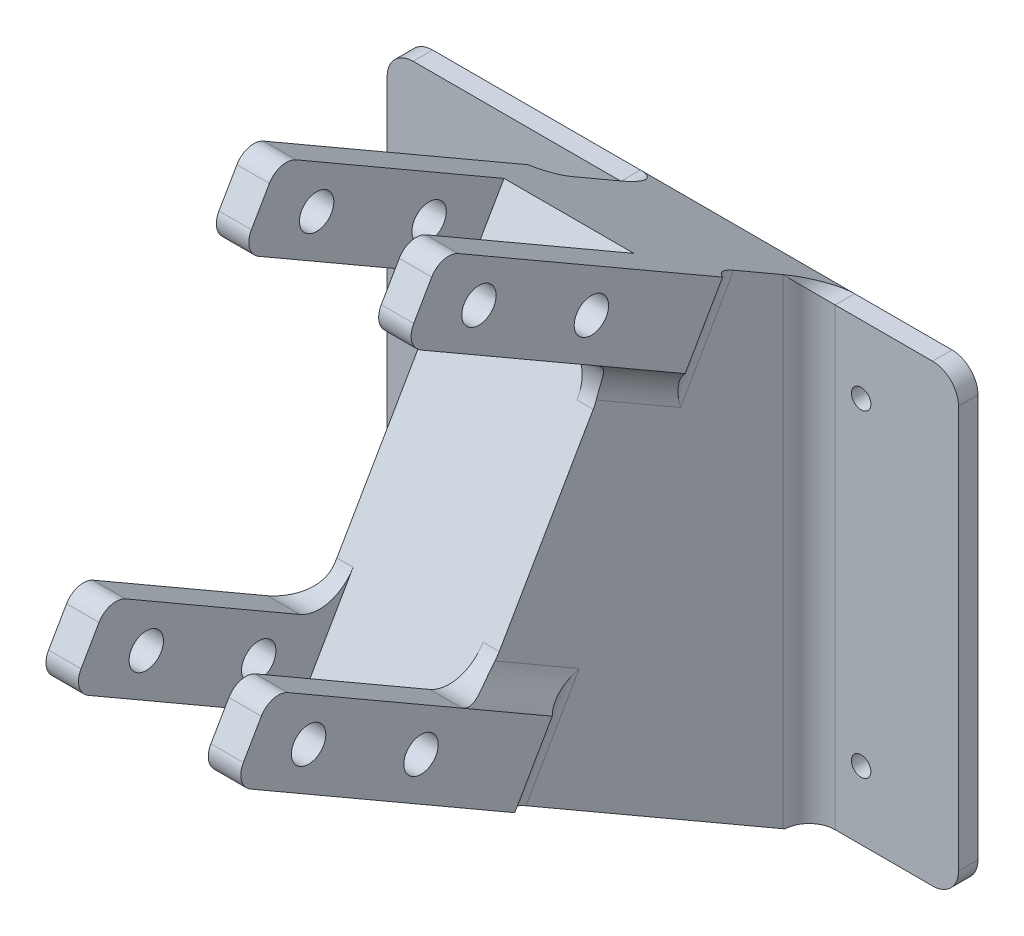
SolidWorks part; units mm, degrees
ref_plane "Piano frontale" through (0, 0, 0) normal (0, 0, 1) x (1, 0, 0)
ref_plane "Piano superiore" through (0, 0, 0) normal (0, 1, 0) x (1, 0, 0)
ref_plane "Piano destro" through (0, 0, 0) normal (1, 0, 0) x (0, 0, -1)
sketch "Schizzo1" plane through (0, 0, 0) normal (0, 0, 1) x (1, 0, 0)
  line L0 (0, 1) -> (0, -49999) construction
  line L1 (-35.5, -35) -> (35.5, -35)
  line L2 (-35.5, -35) -> (-35.5, 35)
  line L3 (-35.5, 35) -> (35.5, 35)
  line L4 (35.5, -35) -> (35.5, 35)
  line L5 (-35.5, -35) -> (35.5, 35) construction
  line L6 (-35.5, 35) -> (35.5, -35) construction
  dimension "D1" = 70
  dimension "D2" = 71
extrude "Estrusione-Estrusione2" add sketch "Schizzo1" along normal blind 6
sketch "Schizzo4" plane through (0, 0, 6) normal (0, 0, 1) x (1, 0, 0)
  line L0 (35.5, 35) -> (-35.5, 35) construction
  line L1 (-12.5, -35) -> (12.5, -35)
  line L2 (-12.5, -35) -> (-12.5, 35)
  line L3 (-12.5, 35) -> (12.5, 35)
  line L4 (12.5, -35) -> (12.5, 35)
  line L5 (-12.5, -35) -> (12.5, 35) construction
  line L6 (-12.5, 35) -> (12.5, -35) construction
  point P0 (0, 0)
  dimension "D1" = 25
extrude "Estrusione-Estrusione12" add sketch "Schizzo4" along normal blind 0.77 contours L4 L3 L2 L1
sketch "Schizzo11" plane through (-12.5, 0, 0) normal (-1, 0, 0) x (0, 0, 1)
  line L0 (6.77, -35) -> (6.77, 35)
  line L1 (6.77, 35) -> (128.0136, 35)
  line L2 (128.0136, 35) -> (6.77, -35)
  dimension "D1" = 60
extrude "Estrusione-Estrusione7" add sketch "Schizzo11" against normal blind 25
sketch "Schizzo12" plane through (12.5, 0, 0) normal (1, 0, 0) x (0, 0, -1)
  line L1 (-36.6652, 35) -> (-36.6652, 49.4681)
  line L2 (-36.6652, 49.4681) -> (-141.5157, 48.15)
  line L4 (-141.5157, 48.15) -> (-142.5043, -5.7309)
  line L5 (-142.5043, -5.7309) -> (-59.5023, -10.4748)
  line L6 (-67.3918, 0) -> (-47.1845, 35) construction
  line L7 (-59.5023, -4.555) -> (-59.5023, -10.4748)
  line L8 (-6.77, -35) -> (-128.0136, 35) construction
  line L9 (-128.0136, 35) -> (-6, 35) construction
  line L10 (-59.5023, -4.555) -> (-36.6652, 35)
  dimension "D1" = 90
  dimension "D2" = 9.11
extrude "Taglio-Estrusione1" cut sketch "Schizzo12" against normal through all
sketch "Schizzo15" plane through (0, 24.6265, 42.6543) normal (0, 0.5, 0.866) x (1, 0, 0)
  line L0 (0, 12.1226) -> (0, 53.7546) construction
  line L1 (-12.5, 11.9783) -> (12.5, 11.9783) construction
  point P4 (0, 11.9783)
sketch "Schizzo18" plane through (0, 0, 0) normal (1, 0, 0) x (0, 0, -1)
  line L0 (-36.6652, 35) -> (0, 35)
  line L1 (0, 35) -> (-27.4989, 50.8765)
  line L2 (-100036.593, -173169.9558) -> (99984.223, 173276.2601) construction
  line L3 (-27.4989, 50.8765) -> (-36.6652, 35)
  dimension "D1" = 90
extrude "Estrusione-Estrusione13" add sketch "Schizzo18" along normal mid plane 25
sketch "Schizzo19" plane through (12.5, 0, 0) normal (1, 0, 0) x (0, 0, -1)
  line L1 (-59.5023, -4.555) -> (-94.1433, 15.445)
  line L2 (-53.7366, 5.4315) -> (-88.3776, 25.4315)
  line L3 (-94.1433, 15.445) -> (-88.3776, 25.4315)
  line L4 (-44.1501, 23.5357) -> (-44.101, 23.5074) construction
  line L5 (-59.5023, -4.555) -> (-27.4989, 50.8765) construction
  line L6 (-59.5023, -4.555) -> (-50.842, -9.555)
  line L7 (-59.5023, -4.555) -> (-53.7366, 5.4315)
  line L8 (-50.842, -9.555) -> (-45.0763, 0.4315)
  line L9 (-53.7366, 5.4315) -> (-45.0763, 0.4315)
  line L10 (-6.77, -35) -> (-59.5023, -4.555) construction
  line L11 (-91.2604, 20.4383) -> (-56.6194, 0.4383) construction
  line L12 (-82.6002, 15.4383) -> (24917.3998, 43316.7085) construction
  line L13 (-65.2797, 5.4383) -> (24934.7203, 43306.7085) construction
  line L14 (-59.5023, -4.555) -> (-50.842, -9.555)
  line L15 (-53.7366, 5.4315) -> (-45.0763, 0.4315)
  line L16 (-59.5023, -4.555) -> (-94.1433, 15.445)
  line L17 (-53.7366, 5.4315) -> (-88.3776, 25.4315)
  line L18 (-59.5023, -4.555) -> (-94.1433, 15.445)
  line L19 (-53.7366, 5.4315) -> (-88.3776, 25.4315)
  line L20 (-59.5023, -4.555) -> (-50.842, -9.555)
  line L21 (-53.7366, 5.4315) -> (-45.0763, 0.4315)
  line L22 (-59.5023, -4.555) -> (-50.842, -9.555)
  line L23 (-53.7366, 5.4315) -> (-45.0763, 0.4315)
  line L24 (-59.5023, -4.555) -> (-94.1433, 15.445)
  line L25 (-53.7366, 5.4315) -> (-88.3776, 25.4315)
  line L26 (-65.0228, 65.8832) -> (-30.3818, 45.8832) construction
  line L27 (-33.2646, 40.89) -> (-67.9056, 60.89)
  line L28 (-27.4989, 50.8765) -> (-62.1399, 70.8765)
  line L29 (-33.2646, 40.89) -> (-24.6044, 35.89)
  line L30 (-27.4989, 50.8765) -> (-18.8386, 45.8765)
  line L31 (-33.2646, 40.89) -> (-24.6044, 35.89)
  line L32 (-27.4989, 50.8765) -> (-18.8386, 45.8765)
  line L33 (-33.2646, 40.89) -> (-67.9056, 60.89)
  line L34 (-27.4989, 50.8765) -> (-62.1399, 70.8765)
  line L35 (-33.2646, 40.89) -> (-67.9056, 60.89)
  line L36 (-27.4989, 50.8765) -> (-62.1399, 70.8765)
  line L37 (-33.2646, 40.89) -> (-24.6044, 35.89)
  line L38 (-27.4989, 50.8765) -> (-18.8386, 45.8765)
  line L39 (-33.2646, 40.89) -> (-24.6044, 35.89)
  line L40 (-18.8386, 45.8765) -> (-24.6044, 35.89)
  line L41 (-27.4989, 50.8765) -> (-33.2646, 40.89)
  line L42 (-27.4989, 50.8765) -> (-18.8386, 45.8765)
  line L43 (-62.1399, 70.8765) -> (-67.9056, 60.89)
  line L44 (-33.2646, 40.89) -> (-67.9056, 60.89)
  line L45 (-27.4989, 50.8765) -> (-62.1399, 70.8765)
  circle A0 centre (-82.6002, 15.4383) radius 2.65
  circle A1 centre (-65.2797, 5.4383) radius 2.65
  circle A2 centre (-39.042, 50.8832) radius 2.65
  circle A3 centre (-56.3625, 60.8832) radius 2.65
  point P9 (-43.5006, 23.1607)
  line M6 (0, 35) -> (-27.4989, 50.8765)
  line M7 (-27.4989, 50.8765) -> (-59.5023, -4.555)
  line M8 (-59.5023, -4.555) -> (-6.77, -35)
  dimension "D5" = 5.3
  dimension "D6" = 5.3
  dimension "D1" = 40
  dimension "D2" = 10
  dimension "D3" = 20
  dimension "D4" = 10
extrude "Estrusione-Estrusione14" add sketch "Schizzo19" along normal mid plane 5 contours L28 L43 L27 A2 A3 M7 | L40 L29 M6 M7 | L3 L1 L2 A1 A0 M7 | L9 L8 M7 M8
mirror "Specchia1" about plane through (0, 0, 0) normal (1, 0, 0) of "Estrusione-Estrusione14"
fillet "Raccordo1" radius 6 12 edges at (11.25, 40.89, 33.2646) (-11.25, 40.89, 33.2646) (-12.5, 40.8832, 21.7215) (-12.5, 38.39, 28.9345) (12.5, 40.8832, 21.7215) (12.5, 38.39, 28.9345) (12.5, -4.5617, 47.9592) (12.5, 2.9315, 49.4064) (11.25, 5.4315, 53.7366) (-11.25, 5.4315, 53.7366) (-12.5, -4.5617, 47.9592) (-12.5, 2.9315, 49.4064)
fillet "Raccordo2" radius 3 8 edges at (12.5, 15.445, 94.1433) (12.5, 25.4315, 88.3776) (-12.5, 70.8765, 62.1399) (-12.5, 60.89, 67.9056) (-12.5, 25.4315, 88.3776) (-12.5, 15.445, 94.1433) (12.5, 60.89, 67.9056) (12.5, 70.8765, 62.1399)
sketch "Schizzo23" plane through (0, 0, 0) normal (0, 0, -1) x (-1, 0, 0)
  line L1 (35.5, 35) -> (52.5, 35)
  line L2 (35.5, 35) -> (35.5, -35)
  line L3 (35.5, -35) -> (52.5, -35)
  line L4 (52.5, 35) -> (52.5, -35)
  dimension "D1" = 70
  dimension "D2" = 17
extrude "Estrusione-Estrusione16" add sketch "Schizzo23" against normal blind 6
sketch "Schizzo20" plane through (0, 0, 0) normal (0, 0, -1) x (-1, 0, 0)
  line L0 (0, 0) -> (-50000, 0) construction
  line L1 (-20.5, 24.5) -> (37.5, 24.5)
  line L2 (-20.5, 24.5) -> (-20.5, -24.5)
  line L3 (-20.5, -24.5) -> (37.5, -24.5)
  line L4 (37.5, 24.5) -> (37.5, -24.5)
  line L5 (-20.5, 24.5) -> (37.5, -24.5) construction
  line L6 (-20.5, -24.5) -> (37.5, 24.5) construction
  circle A0 centre (-20.5, 24.5) radius 1.5
  circle A1 centre (37.5, 24.5) radius 1.5
  circle A2 centre (37.5, -24.5) radius 1.5
  circle A3 centre (-20.5, -24.5) radius 1.5
  point P0 (8.5, 0)
  dimension "D3" = 3
  dimension "D1" = 58
  dimension "D2" = 49
  dimension "D4" = 20.5
extrude "Taglio-Estrusione2" cut sketch "Schizzo20" against normal through all contours L4 A2 L3 | L3 A2 L4 | A0 | A1 | A3
sketch "Schizzo24" plane through (0, 0, 6) normal (0, 0, 1) x (1, 0, 0)
  line L1 (-52.5, 35) -> (-12.5, 35)
  line L2 (-52.5, 35) -> (-52.5, -35)
  line L3 (-52.5, -35) -> (-12.5, -35)
  line L4 (-12.5, 35) -> (-12.5, -35)
  line L5 (12.5, -35) -> (35.5, -35)
  line L6 (12.5, -35) -> (12.5, 35)
  line L7 (12.5, 35) -> (35.5, 35)
  line L8 (35.5, -35) -> (35.5, 35)
extrude "Taglio-Estrusione3" cut sketch "Schizzo24" against normal blind 3
fillet "Raccordo3" radius 4 8 edges at (-12.5, -35, 4.885) (12.5, -35, 4.885) (-52.5, -35, 1.5) (-52.5, 35, 1.5) (35.5, -35, 1.5) (35.5, 35, 1.5) (-12.5, 0, 3) (12.5, 0, 3)
fillet "Raccordo4" radius 4 2 edges at (-12.5, 35, 3.5) (12.5, 35, 3.5)
